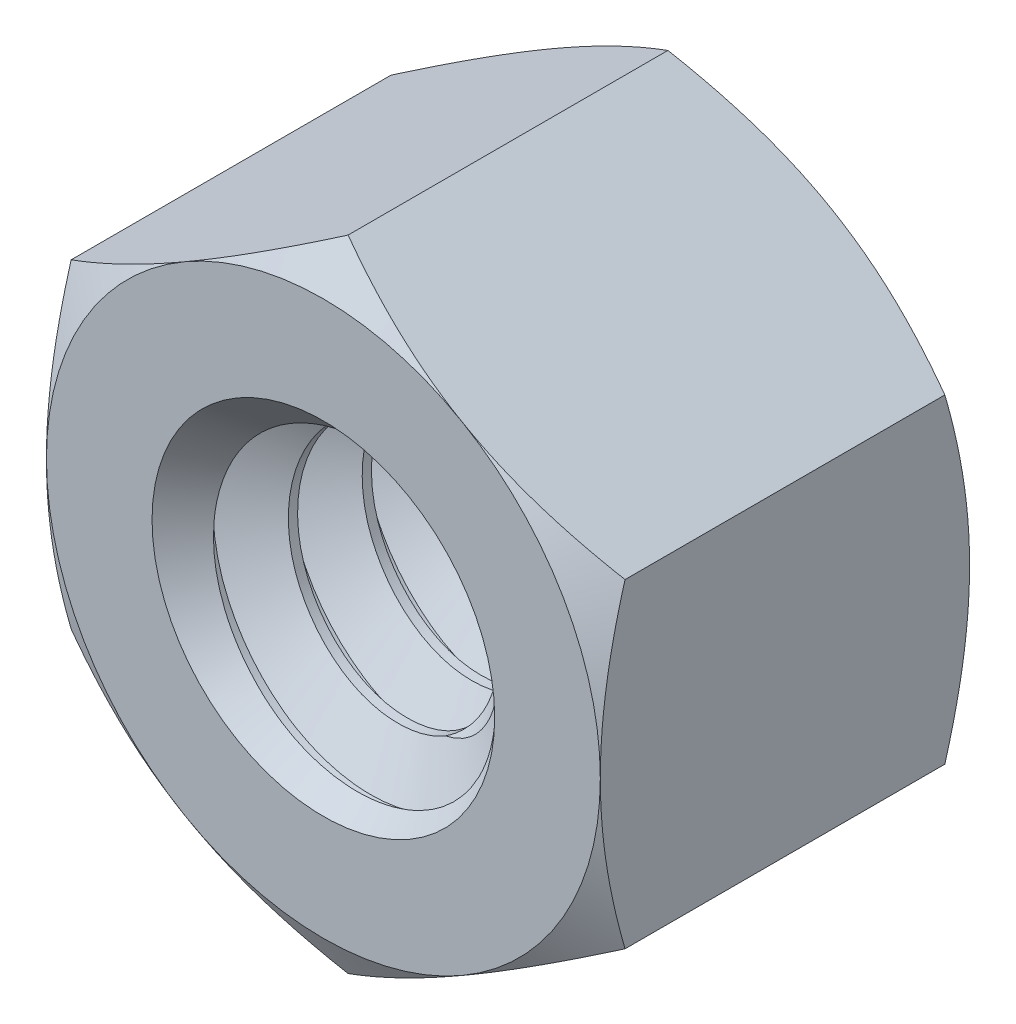
SolidWorks part; units mm, degrees
ref_plane "Front Plane" through (0, 0, 0) normal (0, 0, 1) x (1, 0, 0)
ref_plane "Top Plane" through (0, 0, 0) normal (0, 1, 0) x (1, 0, 0)
ref_plane "Right Plane" through (0, 0, 0) normal (1, 0, 0) x (0, 0, -1)
sketch "Sketch3" plane through (0, 0, 0) normal (1, 0, 0) x (0, 0, -1)
  line L0 (-1.5875, 0) -> (1.5875, 0) construction
  line L1 (0, 2.3813) -> (0, -2.3813) construction
  line L2 (-1.5875, 1.4224) -> (-1.5875, -1.4224) construction
  point P2 (-14.2875, 0)
  point P3 (14.2875, 0)
  dimension "D1" = 15.875
  dimension "Length" = 3.175
  dimension "Min Thread Length" = 15.875
  dimension "Thread Dia" = 2.8448
  dimension "Hex" = 4.7625
sketch "Sketch1" plane through (0, 0, 0) normal (0, 0, 1) x (1, 0, 0)
  line L1 (0, 2.7496) -> (-2.3813, 1.3748)
  line L2 (-2.3813, 1.3748) -> (-2.3813, -1.3748)
  line L3 (-2.3813, -1.3748) -> (0, -2.7496)
  line L4 (0, -2.7496) -> (2.3813, -1.3748)
  line L5 (2.3813, -1.3748) -> (2.3812, 1.3748)
  line L6 (2.3812, 1.3748) -> (0, 2.7496)
  circle A0 centre (0, 0) radius 2.3813 construction
  circle A1 centre (0, 0) radius 1.4224
extrude "Extrude1" add sketch "Sketch1" along normal up to vertex (1.5875 mm away) and the other way up to vertex (1.5875 mm away) up to point (0, 0, 1.5875) other way up to point (0, 0, -1.5875)
sketch "Sketch11" plane through (0, 0, -1.5875) normal (0, 0, -1) x (-1, 0, 0)
  circle A0 centre (0, 0) radius 1.4224 construction
  circle A1 centre (0, 0) radius 1.4224
curve "Helix/Spiral1" pitch 0.635 height 3.81 radius 1.4224 centre (0, 0, -1.5875) axis (0, 0, 1) start towards (0, 1, 0) parameters "Pitch"=0.635
sketch "Sketch12" plane through (0, 0, 0) normal (1, 0, 0) x (0, 0, -1)
  line L0 (2.1431, 1.4224) -> (1.5875, 1.4224)
  line L1 (2.1431, 1.4224) -> (1.905, 1.01)
  line L2 (1.905, 1.01) -> (1.8256, 1.01)
  line L3 (1.8256, 1.01) -> (1.5875, 1.4224)
  line L4 (1.8653, 1.01) -> (1.8653, 1.4224) construction
  line L5 (2.0241, 1.2162) -> (1.7066, 1.2162) construction
  dimension "D1" = 0.0794
  dimension "D2" = 0.3175
  dimension "D3" = 60
sweep "Sweep1" add profiles "Sketch12" path "Helix/Spiral1"
sketch "Sketch6" plane through (0, 0, -1.5875) normal (0, 0, -1) x (-1, 0, 0)
  line L6 (0, 2.7496) -> (-2.3812, 1.3748)
  line L7 (-2.3812, 1.3748) -> (-2.3813, -1.3748)
  line L8 (-2.3813, -1.3748) -> (0, -2.7496)
  line L9 (0, -2.7496) -> (2.3813, -1.3748)
  line L10 (2.3813, -1.3748) -> (2.3813, 1.3748)
  line L11 (2.3813, 1.3748) -> (0, 2.7496)
  line L12 (0, 2.7496) -> (-2.3812, 1.3748)
  line L13 (-2.3812, 1.3748) -> (-2.3813, -1.3748)
  line L14 (-2.3813, -1.3748) -> (0, -2.7496)
  line L15 (0, -2.7496) -> (2.3813, -1.3748)
  line L16 (2.3813, -1.3748) -> (2.3813, 1.3748)
  line L17 (2.3813, 1.3748) -> (0, 2.7496)
  dimension "D1" = 0
extrude "Extrude2" cut sketch "Sketch6" along normal through all
sketch "Sketch7" plane through (0, 0, -1.5875) normal (0, 0, -1) x (-1, 0, 0)
  circle A2 centre (0, 0) radius 1.4732
  circle A3 centre (0, 0) radius 1.4732
  dimension "D1" = 0.0508
extrude "Extrude3" cut sketch "Sketch7" against normal through all draft 43
sketch "Sketch8" plane through (0, 0, -1.5875) normal (0, 0, -1) x (-1, 0, 0)
  circle A0 centre (0, 0) radius 2.3813 construction
  circle A1 centre (0, 0) radius 2.3813
extrude "Extrude4" cut sketch "Sketch8" against normal through all draft 60 flip side to cut
mirror "Mirror1" about plane through (0, 0, 0) normal (0, 0, 1) of "Extrude2", "Extrude3", "Extrude4"
sketch "Sketch9" [suppressed] plane through (0, 0, 0) normal (1, 0, 0) x (0, 0, -1)
  line L1 (-22.225, 3.2258) -> (22.225, 3.2258)
  line L2 (-22.225, 3.2258) -> (-22.225, 0)
  line L3 (-22.225, 0) -> (22.225, 0)
  line L4 (22.225, 3.2258) -> (22.225, 0)
  line L7 (-38.1, 0) -> (38.1, 0) construction
revolve "Revolve" [suppressed] add sketch "Sketch9" angle 360 about L0
sketch "Sketch10" [suppressed] plane through (0, 0, 0) normal (1, 0, 0) x (0, 0, -1)
  line L0 (38.1, 3.175) -> (22.225, 3.175)
  line L1 (-38.1, 3.175) -> (-22.225, 3.175)
  line L2 (22.225, 3.175) -> (22.225, -3.175)
  line L3 (-38.1, -3.2258) -> (-22.225, -3.2258)
  line L4 (-22.225, 3.175) -> (-22.225, -3.2258)
  line L5 (22.225, -3.175) -> (38.1, -3.175)
equation "\"D1@Sketch3\" = \"Min Thread Length@Sketch3\""
equation "\"D3@Helix/Spiral1\" = \"Length@Sketch3\"+\"Pitch@Helix/Spiral1\""
equation "\"D1@Sketch12\" = \"Pitch@Helix/Spiral1\"*.125"
equation "\"D2@Sketch12\" = \"Pitch@Helix/Spiral1\"*.5"
